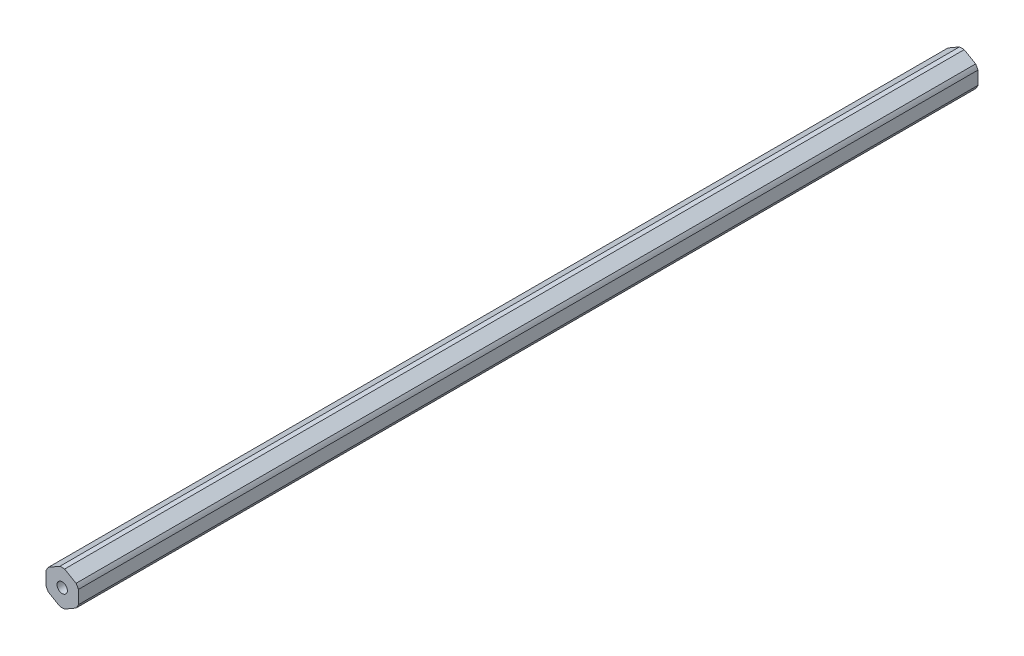
SolidWorks part; units mm, degrees
ref_plane "Front Plane" through (0, 0, 0) normal (0, 0, 1) x (1, 0, 0)
ref_plane "Top Plane" through (0, 0, 0) normal (0, 1, 0) x (1, 0, 0)
ref_plane "Right Plane" through (0, 0, 0) normal (1, 0, 0) x (0, 0, -1)
sketch "Sketch1" plane through (0, 0, 0) normal (0, 0, 1) x (1, 0, 0)
  line L1 (0, 7.3323) -> (-6.35, 3.6662)
  line L2 (-6.35, 3.6662) -> (-6.35, -3.6662)
  line L3 (-6.35, -3.6662) -> (0, -7.3323)
  line L4 (0, -7.3323) -> (6.35, -3.6662)
  line L5 (6.35, -3.6662) -> (6.35, 3.6662)
  line L6 (6.35, 3.6662) -> (0, 7.3323)
  circle A0 centre (0, 0) radius 6.35 construction
  circle A1 centre (0, 0) radius 6.858
  dimension "D1" = 12.7
  dimension "D2" = 13.716
extrude "Boss-Extrude1" add sketch "Sketch1" along normal mid plane 352.425 contours L5 A1 L6 L1 L2 L3 L4 region at (0, 0, 0)
hole_wizard "#10-32 Tapped Hole1" positions "3DSketch1" profile "Sketch2" tap size "#10-32" standard "ANSI Inch"
sketch3d "3DSketch1"
  line L0 (0, 0, 176.2125) -> (0, 0, -176.2125) construction
  line L1 (0, 0, 176.2125) -> (0, 0, -176.2125) construction
  point P0 (0, 0, 176.2125)
  point P4 (0, 0, -176.2125)
sketch "Sketch2" plane through (0, 0, 176.2125) normal (1, 0, 0) x (0, -1, 0)
  line L0 (0, 0) -> (0, 17.5608)
  line L1 (0, 17.5608) -> (2.0193, 16.3474)
  line L2 (2.0193, 16.3474) -> (2.0193, 0)
  line L5 (2.0193, 0) -> (0, 0)
  line L10 (0, 17.5608) -> (-2.0193, 16.3474) construction
  line L11 (0, -6.35) -> (0, 107.95) construction
  dimension "Tap Drill Dia." = 4.0386
  dimension "Tap Drill Depth" = 16.3474
  dimension "Drill Angle" = 118
cosmetic thread "Hole Thread1" parameters "D1"=13.97, "D2"=4.826
cosmetic thread "Hole Thread2" parameters "D1"=13.97, "D2"=4.826
